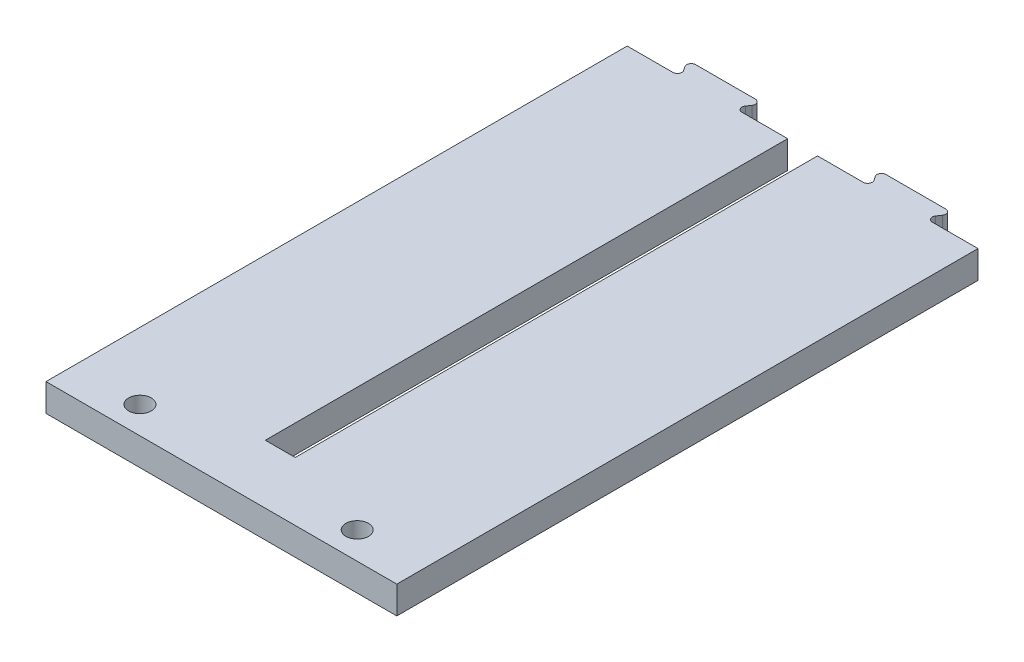
SolidWorks part; units mm, degrees
ref_plane "Front Plane" through (0, 0, 0) normal (0, 0, 1) x (1, 0, 0)
ref_plane "Top Plane" through (0, 0, 0) normal (0, 1, 0) x (1, 0, 0)
ref_plane "Right Plane" through (0, 0, 0) normal (1, 0, 0) x (0, 0, -1)
sketch "Sketch1" plane through (0, 0, 0) normal (0, 1, 0) x (1, 0, 0)
  line L1 (-19.375, 0) -> (19.375, 0)
  line L2 (-19.375, 0) -> (-19.375, 72.5)
  line L3 (-19.375, 72.5) -> (19.375, 72.5)
  line L4 (19.375, 0) -> (19.375, 72.5)
  point P5 (0, 0)
  dimension "D1" = 38.75
  dimension "D2" = 72.5
extrude "Boss-Extrude1" add sketch "Sketch1" along normal blind 3.05 contours L2 | L1 L4 L3 L2 | L4 region at (0, 0, -36.25)
sketch "Sketch4" plane through (0, 3.05, 0) normal (0, 1, 0) x (1, 0, 0)
  line L0 (-19.375, 72.5) -> (19.375, 72.5) construction
  line L2 (-19.375, 0) -> (19.375, 0) construction
  line L3 (1.65, 70.5) -> (-1.65, 70.5)
  line L4 (-1.65, 70.5) -> (-1.65, 69.5)
  line L5 (-1.65, 69.5) -> (1.65, 69.5)
  line L6 (1.65, 69.5) -> (1.65, 70.5)
  line L7 (0, 0) -> (0, 72.5) construction
  line L9 (1.65, 68.3) -> (-1.65, 68.3)
  line L10 (-1.65, 68.3) -> (-1.65, 6.5)
  line L11 (-1.65, 6.5) -> (1.65, 6.5)
  line L12 (1.65, 6.5) -> (1.65, 68.3)
  point P6 (0, 6.5)
  point P10 (0, 70.5)
  point P22 (0, 68.3)
  dimension "D1" = 2
  dimension "D2" = 1
  dimension "D3" = 1.2
  dimension "D4" = 3.3
  dimension "D7" = 6.5
extrude "Cut-Extrude1" cut sketch "Sketch4" against normal through all contours L5 L7 L3 L4 | L11 L7 L9 L10 | L7 L11 L12 L9 | L7 L5 L6 L3 | L6 L3 L4 L5 region at (0.825, 3.05, -70) region at (0.825, 3.05, -37.4) region at (-0.825, 3.05, -37.4) region at (-0.825, 3.05, -70)
sketch "Sketch8" plane through (0, 3.05, 0) normal (0, 1, 0) x (1, 0, 0)
  line L0 (19.375, 0) -> (19.375, 72.5) construction
  line L1 (-19.375, 72.5) -> (19.375, 72.5)
  line L2 (-19.375, 72.5) -> (-19.375, 64.2)
  line L3 (-19.375, 64.2) -> (19.375, 64.2)
  line L4 (19.375, 72.5) -> (19.375, 64.2)
  dimension "D1" = 8.3
extrude "Cut-Extrude5" cut sketch "Sketch8" against normal through all
sketch "Sketch9" plane through (0, 3.05, 0) normal (0, 1, 0) x (1, 0, 0)
  line L0 (-19.375, 64.2) -> (19.375, 64.2) construction
  line L1 (-19.375, 64.2) -> (-19.375, 66.2) construction
  line L2 (19.375, 64.2) -> (19.375, 66.2) construction
  line L3 (-19.375, 66.2) -> (19.375, 66.2) construction
  line L4 (-19.375, 64.2) -> (-13.375, 64.2)
  line L5 (-13.375, 64.2) -> (-14.7625, 66.2)
  line L6 (-14.7625, 66.2) -> (-6.2625, 66.2)
  line L7 (-6.2625, 66.2) -> (-7.65, 64.2)
  line L8 (-7.65, 64.2) -> (-1.65, 64.2)
  line L9 (1.65, 64.2) -> (7.65, 64.2)
  line L10 (7.65, 64.2) -> (6.2625, 66.2)
  line L11 (6.2625, 66.2) -> (14.7625, 66.2)
  line L12 (14.7625, 66.2) -> (13.375, 64.2)
  line L13 (13.375, 64.2) -> (19.375, 64.2)
  line L14 (-13.375, 64.2) -> (-7.65, 64.2)
  line L15 (7.65, 64.2) -> (13.375, 64.2)
  line L16 (-19.375, 66.2) -> (-14.7625, 66.2)
  line L17 (14.7625, 66.2) -> (19.375, 66.2)
  line M1 (-1.65, 64.2) -> (-19.375, 64.2)
  line M5 (19.375, 64.2) -> (1.65, 64.2)
  dimension "D1" = 2
  dimension "D3" = 8.5
  dimension "D4" = 6
extrude "Boss-Extrude3" add sketch "Sketch9" against normal blind 3.05 contours L7 L6 L5 M1 | L12 L11 L10 M5 region at (-10.5125, 3.05, -65.265) region at (10.5125, 3.05, -65.265)
fillet "Fillet2" radius 0.5 8 edges at (13.375, 1.525, -64.2) (-7.65, 1.525, -64.2) (14.7625, 1.525, -66.2) (7.65, 1.525, -64.2) (6.2625, 1.525, -66.2) (-6.2625, 1.525, -66.2) (-14.7625, 1.525, -66.2) (-13.375, 1.525, -64.2)
sketch "Hole Locations" plane through (0, 3.05, 0) normal (0, 1, 0) x (1, 0, 0)
  line L0 (-19.375, 0) -> (19.375, 0) construction
  line L4 (0, 0) -> (0, 70) construction
  circle A0 centre (-12, 3) radius 1 construction
  circle A2 centre (12, 3) radius 1 construction
  dimension "D3" = 2
  dimension "D1" = 12
  dimension "D2" = 3
hole_wizard "Tap Drill for M3x0.5 Tap1" positions "Sketch10" profile "Sketch11" hole size "M3x0.5" standard "ANSI Metric" end condition through all
sketch "Sketch10" plane through (0, 3.05, 0) normal (0, 1, 0) x (1, 0, 0)
  point P0 (-12, 3)
  point P3 (12, 3)
sketch "Sketch11" plane through (-12, 3.05, -3) normal (1, 0, 0) x (0, 0, 1)
  line L0 (0, 0) -> (0, 3.05)
  line L1 (0, 3.05) -> (1.25, 3.05)
  line L2 (1.25, 3.05) -> (1.25, 0)
  line L5 (1.25, 0) -> (0, 0)
  line L11 (0, -6.35) -> (0, 107.95) construction
  dimension "Thru Hole Dia." = 2.5
  dimension "Thru Hole Depth" = 3.05
